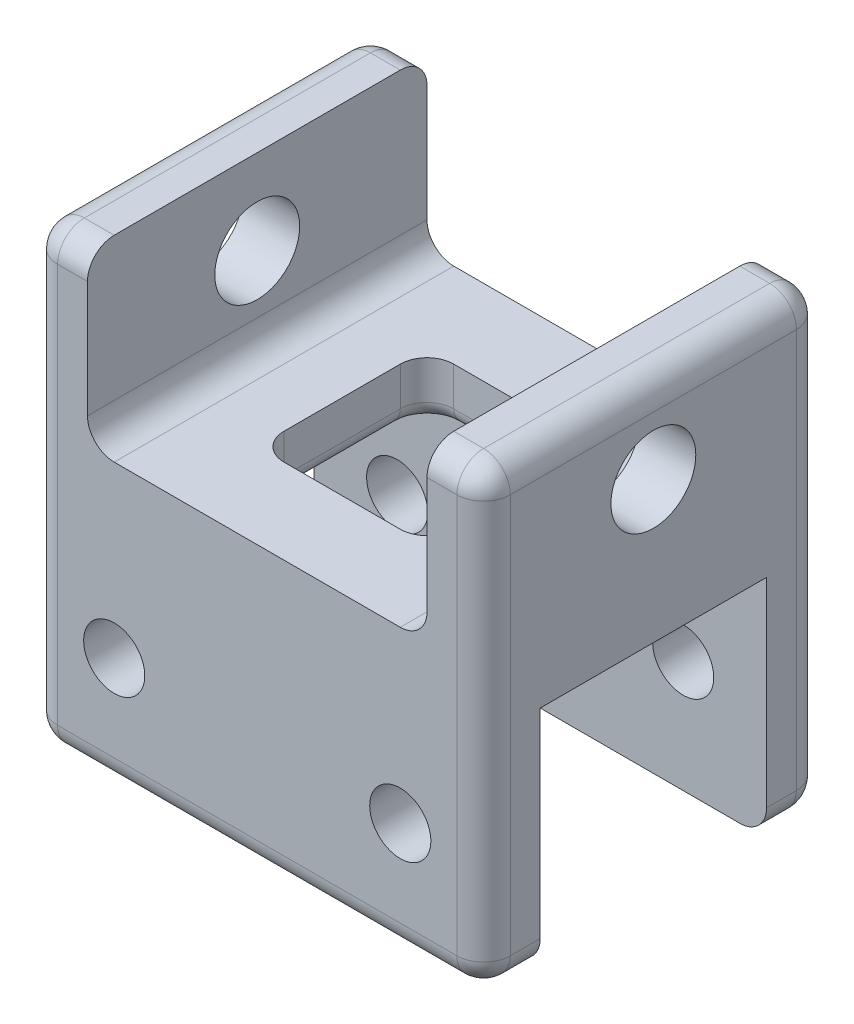
SolidWorks part; units mm, degrees
ref_plane "Front Plane" through (0, 0, 0) normal (0, 0, 1) x (1, 0, 0)
ref_plane "Top Plane" through (0, 0, 0) normal (0, 1, 0) x (1, 0, 0)
ref_plane "Right Plane" through (0, 0, 0) normal (1, 0, 0) x (0, 0, -1)
sketch "Sketch1" plane through (0, 0, 0) normal (0, 1, 0) x (1, 0, 0)
  line L1 (-109.7405, 60.0061) -> (-58.9405, 60.0061)
  line L2 (-109.7405, 60.0061) -> (-109.7405, 21.9061)
  line L3 (-109.7405, 21.9061) -> (-58.9405, 21.9061)
  line L4 (-58.9405, 60.0061) -> (-58.9405, 21.9061)
  line L5 (-109.7405, 60.0061) -> (-58.9405, 21.9061) construction
  line L6 (-109.7405, 21.9061) -> (-58.9405, 60.0061) construction
  point P0 (-84.3405, 40.9561)
  dimension "D1" = 50.8
  dimension "D2" = 38.1
extrude "Boss-Extrude1" add sketch "Sketch1" along normal blind 31.75
sketch "Sketch2" plane through (-58.9405, 0, 0) normal (1, 0, 0) x (0, 0, -1)
  line L0 (40.9561, 31.75) -> (40.9561, 0) construction
  line L1 (21.9061, 31.75) -> (60.0061, 31.75) construction
  line L2 (21.9061, 0) -> (60.0061, 0) construction
  line L3 (21.9061, 25.4) -> (60.0061, 25.4) construction
  line L4 (21.9061, 31.75) -> (21.9061, 0) construction
  line L5 (60.0061, 31.75) -> (60.0061, 0) construction
  line L7 (28.2561, 25.4) -> (53.6561, 25.4)
  line L8 (28.2561, 25.4) -> (28.2561, 0)
  line L9 (28.2561, 0) -> (53.6561, 0)
  line L10 (53.6561, 25.4) -> (53.6561, 0)
  dimension "D1" = 6.35
  dimension "D2" = 6.35
  dimension "D3" = 6.35
  dimension "D4" = 25.4
extrude "Cut-Extrude1" cut sketch "Sketch2" against normal through all
sketch "Sketch3" plane through (0, 31.75, 0) normal (0, 1, 0) x (1, 0, 0)
  line L0 (-58.9405, 60.0061) -> (-109.7405, 60.0061) construction
  line L1 (-103.3905, 60.0061) -> (-109.7405, 60.0061)
  line L2 (-103.3905, 60.0061) -> (-103.3905, 21.9061)
  line L3 (-103.3905, 21.9061) -> (-109.7405, 21.9061)
  line L4 (-109.7405, 60.0061) -> (-109.7405, 21.9061)
  dimension "D1" = 6.35
extrude "Boss-Extrude2" add sketch "Sketch3" along normal blind 19.05
sketch "Sketch4" plane through (0, 31.75, 0) normal (0, 1, 0) x (1, 0, 0)
  line L0 (-103.3905, 21.9061) -> (-58.9405, 21.9061) construction
  line L1 (-58.9405, 60.0061) -> (-65.2905, 60.0061)
  line L2 (-58.9405, 60.0061) -> (-58.9405, 21.9061)
  line L3 (-58.9405, 21.9061) -> (-65.2905, 21.9061)
  line L4 (-65.2905, 60.0061) -> (-65.2905, 21.9061)
  dimension "D1" = 6.35
extrude "Boss-Extrude3" add sketch "Sketch4" along normal blind 19.05
sketch "Sketch5" plane through (-103.3905, 0, 0) normal (1, 0, 0) x (0, 0, -1)
  line L0 (40.9561, 31.75) -> (40.9561, 50.8) construction
  line L1 (21.9061, 31.75) -> (60.0061, 31.75) construction
  line L2 (21.9061, 50.8) -> (60.0061, 50.8) construction
  line L3 (21.9061, 41.275) -> (60.0061, 41.275) construction
  line L4 (21.9061, 50.8) -> (21.9061, 31.75) construction
  line L5 (60.0061, 50.8) -> (60.0061, 31.75) construction
  circle A0 centre (40.9561, 41.275) radius 4.7625
  dimension "D1" = 9.525
extrude "Cut-Extrude2" cut sketch "Sketch5" against normal through all and the other way through all
fillet "Fillet1" radius 3 6 edges at (-106.5655, 50.8, -60.0061) (-106.5655, 50.8, -21.9061) (-62.1155, 50.8, -21.9061) (-62.1155, 50.8, -60.0061) (-65.2905, 31.75, -40.9561)
sketch "Sketch6" plane through (0, 0, -60.0061) normal (0, 0, -1) x (-1, 0, 0)
  line L0 (58.9405, 12.7) -> (109.7405, 12.7) construction
  line L1 (58.9405, 47.8) -> (58.9405, 0) construction
  line L2 (109.7405, 47.8) -> (109.7405, 0) construction
  line L3 (68.2905, 31.75) -> (68.2905, 0) construction
  line L4 (58.9405, 0) -> (109.7405, 0) construction
  line L5 (100.3905, 31.75) -> (100.3905, 0) construction
  circle A0 centre (68.2905, 12.7) radius 3.429
  dimension "D1" = 12.7
extrude "Cut-Extrude3" cut sketch "Sketch6" against normal through all
sketch "Sketch7" plane through (0, 0, -60.0061) normal (0, 0, -1) x (-1, 0, 0)
  line L0 (100.3905, 31.75) -> (100.3905, 0) construction
  line L1 (58.9405, 0) -> (109.7405, 0) construction
  line L2 (71.7195, 12.7) -> (109.7405, 12.7) construction
  line L3 (109.7405, 47.8) -> (109.7405, 0) construction
  circle A0 centre (68.2905, 12.7) radius 3.429 construction
  circle A1 centre (100.3905, 12.7) radius 3.429
extrude "Cut-Extrude4" cut sketch "Sketch7" against normal through all
sketch "Sketch8" plane through (0, 31.75, 0) normal (0, 1, 0) x (1, 0, 0)
  line L0 (-84.3405, 60.0061) -> (-84.3405, 21.9061) construction
  line L1 (-68.2905, 60.0061) -> (-100.3905, 60.0061) construction
  line L2 (-100.3905, 21.9061) -> (-68.2905, 21.9061) construction
  line L4 (-74.8155, 31.4311) -> (-93.8655, 31.4311)
  line L5 (-74.8155, 31.4311) -> (-74.8155, 50.4811)
  line L6 (-74.8155, 50.4811) -> (-93.8655, 50.4811)
  line L7 (-93.8655, 31.4311) -> (-93.8655, 50.4811)
  line L8 (-74.8155, 31.4311) -> (-93.8655, 50.4811) construction
  line L9 (-74.8155, 50.4811) -> (-93.8655, 31.4311) construction
  point P6 (-84.3405, 40.9561)
  dimension "D1" = 19.05
  dimension "D2" = 19.05
extrude "Cut-Extrude5" cut sketch "Sketch8" against normal through all
fillet "Fillet2" radius 3 2 edges at (-93.8655, 28.575, -50.4811) (-93.8655, 28.575, -31.4311)
fillet "Fillet3" radius 3 2 edges at (-74.8155, 28.575, -31.4311) (-74.8155, 28.575, -50.4811)
fillet "Fillet4" radius 3 7 edges at (-58.9405, 23.9, -21.9061) (-58.9405, 49.9213, -22.7848) (-58.9405, 50.8, -40.9561) (-58.9405, 49.9213, -59.1274) (-58.9405, 23.9, -60.0061) (-84.3405, 0, -21.9061) (-84.3405, 0, -60.0061)
fillet "Fillet5" radius 3 9 edges at (-109.7405, 0, -26.5811) (-109.7405, 0.8787, -22.7848) (-109.7405, 25.4, -21.9061) (-109.7405, 49.9213, -22.7848) (-109.7405, 50.8, -40.9561) (-109.7405, 49.9213, -59.1274) (-109.7405, 0, -55.3311) (-109.7405, 0.8787, -59.1274) (-109.7405, 25.4, -60.0061)
fillet "Fillet6" radius 3 4 edges at (-59.8192, 0.8787, -22.7848) (-59.8192, 0.8787, -59.1274) (-58.9405, 0, -26.5811) (-58.9405, 0, -55.3311)
fillet "Fillet7" radius 2 8 edges at (-75.6942, 25.4, -49.6024) (-74.8155, 25.4, -40.9561) (-75.6942, 25.4, -32.3098) (-84.3405, 25.4, -31.4311) (-92.9868, 25.4, -32.3098) (-93.8655, 25.4, -40.9561) (-92.9868, 25.4, -49.6024) (-84.3405, 25.4, -50.4811)
